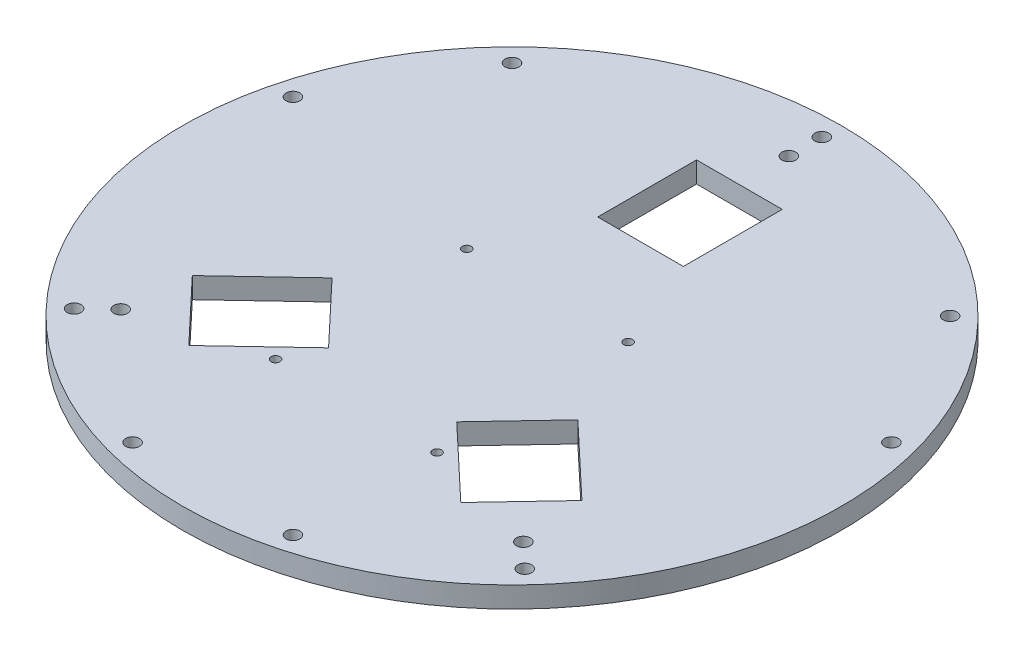
SolidWorks part; units mm, degrees
ref_plane "Front Plane" through (0, 0, 0) normal (0, 0, 1) x (1, 0, 0)
ref_plane "Top Plane" through (0, 0, 0) normal (0, 1, 0) x (1, 0, 0)
ref_plane "Right Plane" through (0, 0, 0) normal (1, 0, 0) x (0, 0, -1)
sketch "Sketch1" plane through (0, 0, 0) normal (0, 1, 0) x (1, 0, 0)
  line L0 (0, 100) -> (0, -100) construction
  line L1 (-24.5, 37.25) -> (24.5, 37.25) construction
  line L2 (-24.5, 37.25) -> (-24.5, -47.25) construction
  line L3 (-24.5, -47.25) -> (24.5, -47.25) construction
  line L4 (24.5, 37.25) -> (24.5, -47.25) construction
  line L5 (-24.5, 37.25) -> (24.5, -47.25) construction
  line L6 (-24.5, -47.25) -> (24.5, 37.25) construction
  line L7 (-24.5, -47.25) -> (24.5, -47.25) construction
  line L8 (-24.5, -47.25) -> (-24.5, 10.75) construction
  line L9 (-24.5, 10.75) -> (24.5, 10.75) construction
  line L10 (24.5, -47.25) -> (24.5, 10.75) construction
  line L11 (0, 0) -> (91.8216, 39.608) construction
  line L12 (0, 0) -> (-91.8216, 39.608) construction
  line L13 (19.4464, -36.2193) -> (59.1099, -37.8948) construction
  line L14 (-13, 69) -> (13, 69)
  line L15 (-13, 69) -> (-13, 39)
  line L16 (-13, 39) -> (13, 39)
  line L17 (13, 69) -> (13, 39)
  line L18 (-13, 69) -> (13, 39) construction
  line L19 (-13, 39) -> (13, 69) construction
  line L20 (41.2676, -56.8065) -> (37.2887, -17.3076) construction
  line L21 (59.1099, -37.8948) -> (37.2887, -17.3076)
  line L22 (19.4464, -36.2193) -> (37.2887, -17.3076)
  line L23 (41.2676, -56.8065) -> (19.4464, -36.2193)
  line L24 (41.2676, -56.8065) -> (59.1099, -37.8948)
  line L25 (-37.2887, -17.3076) -> (-41.2676, -56.8065) construction
  line L26 (-59.1099, -37.8948) -> (-19.4464, -36.2193) construction
  line L27 (-41.2676, -56.8065) -> (-19.4464, -36.2193)
  line L28 (-37.2887, -17.3076) -> (-19.4464, -36.2193)
  line L29 (-59.1099, -37.8948) -> (-37.2887, -17.3076)
  line L30 (-59.1099, -37.8948) -> (-41.2676, -56.8065)
  circle A0 centre (0, 0) radius 100
  circle A1 centre (-24.5, -47.25) radius 1.35
  circle A2 centre (24.5, -47.25) radius 1.35
  circle A3 centre (24.5, 10.75) radius 1.35
  circle A4 centre (-24.5, 10.75) radius 1.35
  circle A5 centre (0, 94) radius 2.1
  circle A6 centre (0, 84) radius 2.1
  circle A7 centre (61.0994, -57.6443) radius 2.1
  circle A8 centre (68.3731, -64.5067) radius 2.1
  circle A9 centre (-68.3731, -64.5067) radius 2.1
  circle A10 centre (-61.0994, -57.6443) radius 2.1
  point P29 (0, 54)
  point P38 (39.2782, -37.057)
  point P43 (-39.2782, -37.057)
  point P44 (0, -5)
  point P46 (0, 0)
  dimension "D1" = 200
  dimension "D3" = 2.7
  dimension "D6" = 4.2
  dimension "D2" = 49
  dimension "D4" = 58
  dimension "D5" = 84.5
  dimension "D7" = 6
  dimension "D8" = 10
  dimension "D9" = 66.667
  dimension "D10" = 30
  dimension "D11" = 26
  dimension "D12" = 15
  dimension "D13" = 5
extrude "Boss-Extrude1" add sketch "Sketch1" along normal blind 6.35
sketch "Sketch2" plane through (0, 6.35, 0) normal (0, 1, 0) x (1, 0, 0)
  line L0 (0, 0) -> (0, -100) construction
  line L1 (0, 0) -> (-25.8819, -96.5926) construction
  circle A0 centre (0, 0) radius 100 construction
  circle A1 centre (-24.329, -90.797) radius 2.1
  circle A2 centre (24.329, -90.797) radius 2.1
  circle A3 centre (-66.468, 66.468) radius 2.1
  circle A4 centre (-90.797, 24.329) radius 2.1
  circle A5 centre (90.797, 24.329) radius 2.1
  circle A6 centre (66.468, 66.468) radius 2.1
  point P22 (0, 0)
  dimension "D4" = 4.2
  dimension "D1" = 15
  dimension "D5" = 6
  dimension "D6" = 3
extrude "Cut-Extrude1" cut sketch "Sketch2" against normal up to surface (6.35 mm away) up to face at (39.2782, 0, 37.057)
